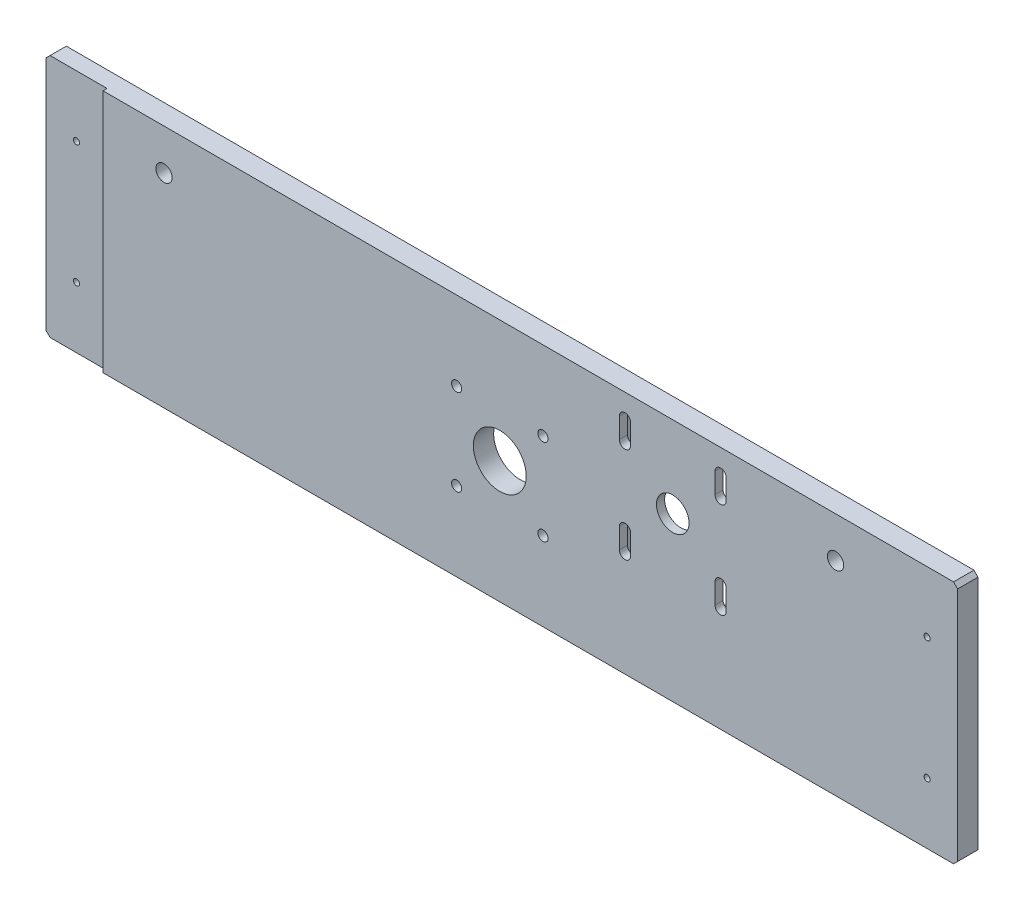
SolidWorks part; units mm, degrees
ref_plane "Piano frontale" through (0, 0, 0) normal (0, 0, 1) x (1, 0, 0)
ref_plane "Piano superiore" through (0, 0, 0) normal (0, 1, 0) x (1, 0, 0)
ref_plane "Piano destro" through (0, 0, 0) normal (1, 0, 0) x (0, 0, -1)
sketch "Schizzo1" plane through (0, 0, 0) normal (0, 0, 1) x (1, 0, 0)
  line L0 (225, 120) -> (225, 0) construction
  line L1 (2, 0) -> (448, 0)
  line L2 (0, 2) -> (0, 118)
  line L3 (2, 120) -> (448, 120)
  line L4 (450, 2) -> (450, 118)
  line L7 (225, 60) -> (243.5099, 60) construction
  line L8 (459.2931, 100) -> (370.8276, 100) construction
  line L9 (225, 60) -> (194.6932, 90.3068) construction
  line L21 (0, 118) -> (2, 120)
  line L22 (2, 0) -> (0, 2)
  line L23 (448, 0) -> (450, 2)
  line L24 (448, 120) -> (450, 118)
  line L25 (225, 60) -> (450, 60) construction
  line L26 (344.754, 80) -> (282.8483, 80) construction
  line L27 (333.5, 108.5) -> (333.5, 98.5) construction
  line L28 (330.75, 108.5) -> (330.75, 98.5)
  line L29 (336.25, 108.5) -> (336.25, 98.5)
  line L30 (286.5, 108.5) -> (286.5, 98.5) construction
  line L31 (289.25, 108.5) -> (289.25, 98.5)
  line L32 (283.75, 108.5) -> (283.75, 98.5)
  line L33 (333.5, 51.5) -> (333.5, 61.5) construction
  line L34 (330.75, 51.5) -> (330.75, 61.5)
  line L35 (336.25, 51.5) -> (336.25, 61.5)
  line L36 (286.5, 51.5) -> (286.5, 61.5) construction
  line L37 (289.25, 51.5) -> (289.25, 61.5)
  line L38 (283.75, 51.5) -> (283.75, 61.5)
  line L42 (310, 120) -> (310, 0) construction
  circle A0 centre (225, 60) radius 13
  circle A1 centre (225, 60) radius 30 construction
  circle A2 centre (246.2132, 81.2132) radius 2.5
  circle A3 centre (390, 100) radius 4
  circle A4 centre (246.2132, 38.7868) radius 2.5
  circle A5 centre (203.7868, 38.7868) radius 2.5
  circle A10 centre (60, 100) radius 4
  circle A11 centre (15, 30) radius 1.5
  circle A12 centre (435, 30) radius 1.5
  circle A13 centre (203.7868, 81.2132) radius 2.5
  circle A17 centre (435, 90) radius 1.5
  circle A18 centre (15, 90) radius 1.5
  arc A19 (330.75, 108.5) -> (336.25, 108.5) centre (333.5, 108.5) cw
  arc A20 (336.25, 98.5) -> (330.75, 98.5) centre (333.5, 98.5) cw
  arc A21 (289.25, 108.5) -> (283.75, 108.5) centre (286.5, 108.5) ccw
  arc A22 (283.75, 98.5) -> (289.25, 98.5) centre (286.5, 98.5) ccw
  arc A23 (330.75, 51.5) -> (336.25, 51.5) centre (333.5, 51.5) ccw
  arc A24 (336.25, 61.5) -> (330.75, 61.5) centre (333.5, 61.5) ccw
  arc A25 (289.25, 51.5) -> (283.75, 51.5) centre (286.5, 51.5) cw
  arc A26 (283.75, 61.5) -> (289.25, 61.5) centre (286.5, 61.5) cw
  circle A27 centre (310, 80) radius 8
  point P0 (0, 0)
  point P1 (450, 120)
  point P2 (0, 120)
  point P3 (450, 0)
  point P9 (203.7868, 81.2132)
  point P13 (203.7868, 81.2132)
  point P80 (310, 80)
  point P83 (333.5, 103.5)
  point P90 (286.5, 103.5)
  point P97 (333.5, 56.5)
  point P104 (286.5, 56.5)
  dimension "D4" = 26
  dimension "D10" = 8
  dimension "D15" = 3
  dimension "D17" = 5
  dimension "D25" = 16
  dimension "D8" = 45
  dimension "D1" = 120
  dimension "D2" = 450
  dimension "D3" = 60
  dimension "D7" = 20
  dimension "D12" = 60
  dimension "D14" = 30
  dimension "D16" = 15
  dimension "D18" = 40
  dimension "D23" = 23.5
  dimension "D24" = 23.5
  dimension "D26" = 5.5
  dimension "D27" = 10
  dimension "D29" = 140
extrude "Estrusione-Estrusione1" add sketch "Schizzo1" against normal blind 10
sketch "Schizzo2" plane through (0, 0, 0) normal (0, 0, 1) x (1, 0, 0)
  line L0 (448, 120) -> (2, 120) construction
  line L1 (30, 120) -> (0, 120)
  line L2 (30, 120) -> (30, 0)
  line L3 (30, 0) -> (0, 0)
  line L4 (0, 120) -> (0, 0)
  line L5 (315.2194, 120) -> (315.2194, -23.5993) construction
  line L6 (630.4389, 120) -> (630.4389, 0)
  line L7 (600.4389, 0) -> (630.4389, 0)
  line L8 (600.4389, 120) -> (600.4389, 0)
  line L9 (600.4389, 120) -> (630.4389, 120)
  dimension "D1" = 30
extrude "Taglio-Estrusione1" cut sketch "Schizzo2" against normal blind 2
sketch "Schizzo3" plane through (0, 0, -10) normal (0, 0, -1) x (-1, 0, 0)
  line L0 (-310, 80) -> (-310, 120) construction
  line L1 (-448, 120) -> (-2, 120) construction
  line L2 (-310, 80) -> (-342.9696, 80) construction
  line L4 (-280, 44) -> (-340, 44)
  line L5 (-280, 44) -> (-280, 116)
  line L6 (-280, 116) -> (-340, 116)
  line L7 (-340, 44) -> (-340, 116)
  line L8 (-280, 44) -> (-340, 116) construction
  line L9 (-280, 116) -> (-340, 44) construction
  dimension "D1" = 60
  dimension "D2" = 72
extrude "Taglio-Estrusione2" cut sketch "Schizzo3" against normal blind 6
